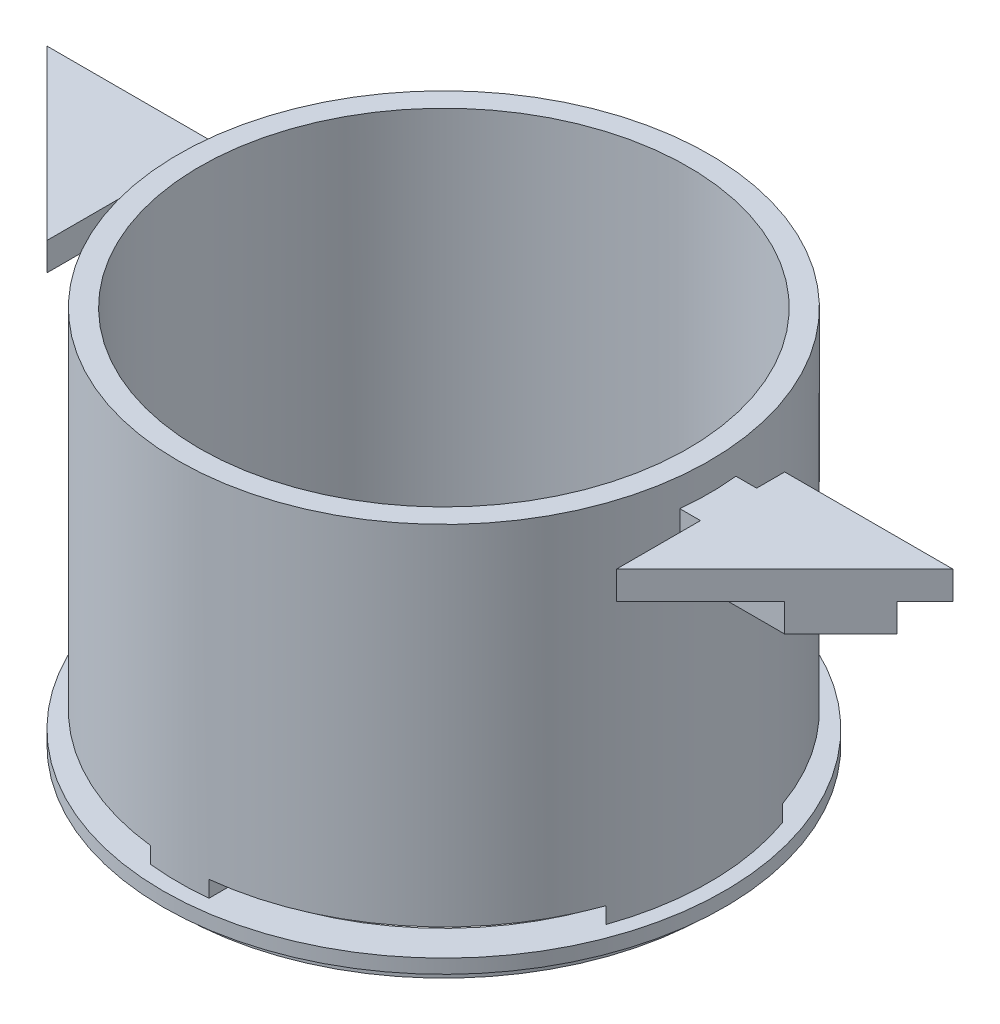
SolidWorks part; units mm, degrees
ref_plane "Front Plane" through (0, 0, 0) normal (0, 0, 1) x (1, 0, 0)
ref_plane "Top Plane" through (0, 0, 0) normal (0, 1, 0) x (1, 0, 0)
ref_plane "Right Plane" through (0, 0, 0) normal (1, 0, 0) x (0, 0, -1)
sketch "Sketch1" plane through (0, 0, 0) normal (0, 1, 0) x (1, 0, 0)
  circle A0 centre (0, 0) radius 60.071
  dimension "D2" = 120.142
extrude "Boss-Extrude1" add sketch "Sketch1" along normal blind 88.9
sketch "Sketch2" plane through (0, 88.9, 0) normal (0, 1, 0) x (1, 0, 0)
  circle A0 centre (0, 0) radius 55.245
  dimension "D1" = 110.49
extrude "Cut-Extrude1" cut sketch "Sketch2" against normal through all
sketch "Sketch6" plane through (0, 0, 0) normal (0, 0, 1) x (1, 0, 0)
  line L0 (-60.071, 88.9) -> (-60.071, 0) construction
  line L1 (-56.642, 10.033) -> (-6.604, 10.033)
  line L2 (-56.642, 10.033) -> (-56.642, 6.35)
  line L3 (-56.642, 6.35) -> (-6.604, 6.35)
  line L7 (-55.245, 0) -> (55.245, 0) construction
  line L8 (-6.604, 10.033) -> (-6.604, 6.35)
  line L9 (0, 0) -> (0, 21.9448) construction
  line L10 (6.604, 10.033) -> (6.604, 6.35)
  line L11 (56.642, 6.35) -> (6.604, 6.35)
  line L12 (56.642, 10.033) -> (6.604, 10.033)
  line L13 (56.642, 10.033) -> (56.642, 6.35)
  dimension "D2" = 3.429
  dimension "D3" = 3.683
  dimension "D4" = 6.35
  dimension "D1" = 6.604
extrude "Cut-Extrude4" cut sketch "Sketch6" against normal through all both and the other way through all
ref_plane "Plane1" through (0, 69.85, 0) normal (0, 1, 0) x (1, 0, 0)
sketch "Sketch10" plane through (0, 0, 0) normal (0, 1, 0) x (1, 0, 0)
  circle A0 centre (0, 0) radius 63.5
  circle A1 centre (0, 0) radius 60.071 construction
  circle A2 centre (0, 0) radius 60.071
  dimension "D1" = 127
extrude "Boss-Extrude7" add sketch "Sketch10" along normal blind 3.175 from offset 3.175
sketch "Sketch9" plane through (0, 69.85, 0) normal (0, 1, 0) x (1, 0, 0)
  line L1 (-83.4526, -6.35) -> (-54.8788, -6.35)
  line L3 (-96.1526, 6.35) -> (-54.8788, 6.35)
  line L7 (-96.1526, 6.35) -> (-83.4526, -6.35)
  circle A0 centre (0, 0) radius 55.245 construction
  arc A1 (-54.8788, 6.35) -> (-54.8788, -6.35) centre (0, 0) ccw
  point P0 (0, 0)
  point P2 (-89.8026, 0)
  dimension "D1" = 96.1526
  dimension "D2" = 45
  dimension "D4" = 12.7
extrude "Boss-Extrude6" add sketch "Sketch9" along normal blind 12.7
sketch "Sketch11" plane through (0, 82.55, 0) normal (0, 1, 0) x (1, 0, 0)
  line L0 (-64.4026, -25.4) -> (-64.4026, 12.7)
  line L1 (-64.4026, 12.7) -> (-102.5026, 12.7)
  line L2 (-102.5026, 12.7) -> (-64.4026, -25.4)
  line L3 (-96.1526, 6.35) -> (-83.4526, -6.35) construction
  line L4 (-59.7344, 6.35) -> (-96.1526, 6.35) construction
  line L5 (-83.4526, -6.35) -> (-59.7344, -6.35) construction
  dimension "D1" = 6.35
  dimension "D2" = 19.05
extrude "Boss-Extrude8" add sketch "Sketch11" against normal blind 6.35
mirror "Mirror1" about plane through (0, 0, 0) normal (1, 0, 0) of "Boss-Extrude6", "Boss-Extrude8"
equation "\"tightTol\" = 0.005in"
equation "\"normTol\"= 0.01in"
equation "\"looseTol\"= 0.02in"
equation "\"D2@Sketch6\"=\"normTol\"+0.125000in"
equation "\"D1@Sketch6\"=\"normTol\"+0.250000in"
equation "\"D3@Sketch6\"=\"looseTol\"+0.125000in"
equation "\"D2@Sketch1\"=4.750000in-\"looseTol\""
